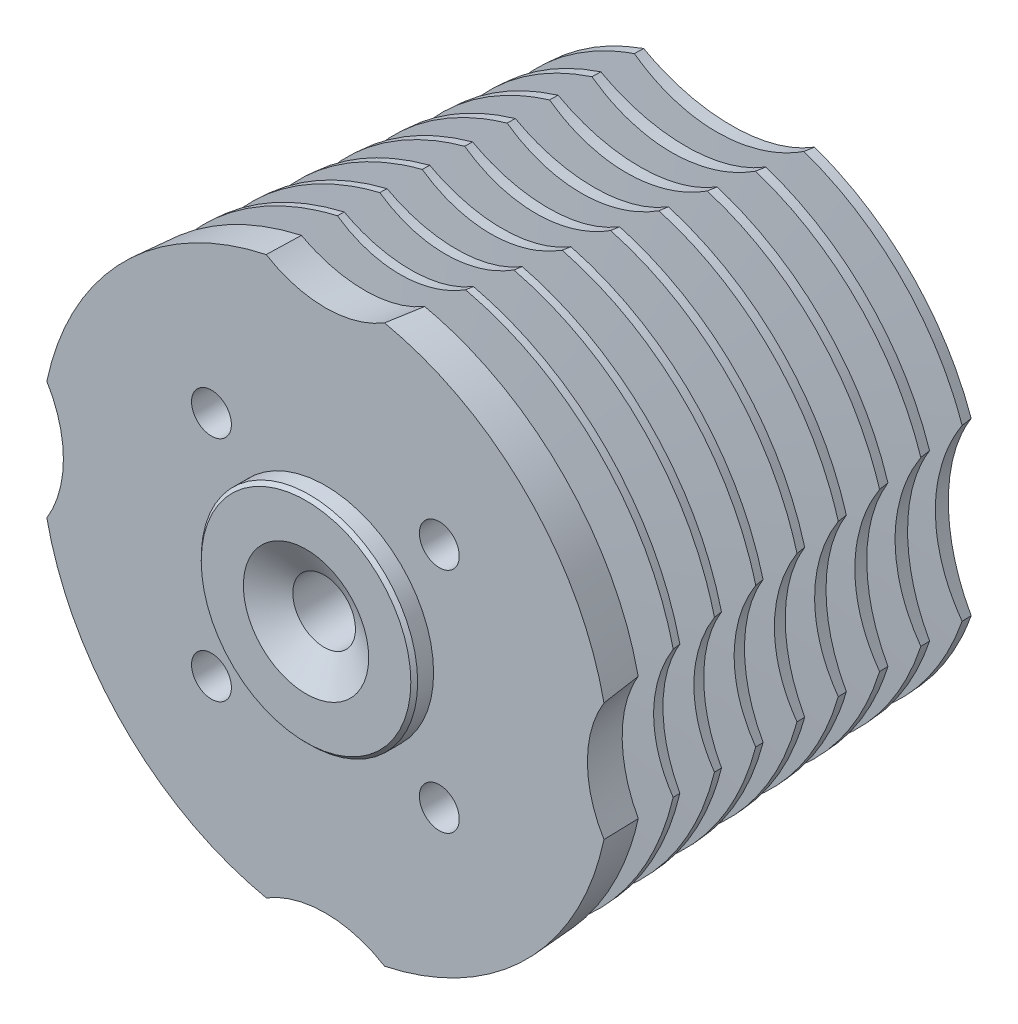
SolidWorks part; units mm, degrees
ref_plane "Face" through (0, 0, 0) normal (0, 0, 1) x (1, 0, 0)
ref_plane "Dessus" through (0, 0, 0) normal (0, 1, 0) x (1, 0, 0)
ref_plane "Droite" through (0, 0, 0) normal (1, 0, 0) x (0, 0, -1)
sketch "Esquisse1" plane through (0, 0, 0) normal (0, 0, 1) x (1, 0, 0)
  circle A0 centre (0, 0) radius 9.5
  dimension "D1" = 19
extrude "Base-Extrusion" add sketch "Esquisse1" along normal blind 1.7
sketch "Esquisse2" plane through (0, 0, 0) normal (0, 0, -1) x (-1, 0, 0)
  arc A0 (24.4545, 5.1938) -> (5.1938, 24.4545) centre (0, 0) ccw
  arc A1 (-5.1938, 24.4545) -> (5.1938, 24.4545) centre (0, 33) ccw
  arc A2 (5.1938, -24.4545) -> (-5.1938, -24.4545) centre (0, -33) ccw
  arc A3 (24.4545, 5.1938) -> (24.4545, -5.1938) centre (33, 0) ccw
  arc A4 (-24.4545, -5.1938) -> (-24.4545, 5.1938) centre (-33, 0) ccw
  arc A5 (-5.1938, 24.4545) -> (-24.4545, 5.1938) centre (0, 0) ccw
  arc A6 (-24.4545, -5.1938) -> (-5.1938, -24.4545) centre (0, 0) ccw
  arc A7 (5.1938, -24.4545) -> (24.4545, -5.1938) centre (0, 0) ccw
  dimension "D1" = 50
  dimension "D2" = 20
  dimension "D3" = 33
  dimension "D4" = 33
  dimension "D5" = 66
  dimension "D6" = 66
ref_plane "Plan1" through (0, 0, -36) normal (0, 0, 1) x (1, 0, 0)
sketch "Esquisse3" plane through (0, 0, -36) normal (0, 0, 1) x (1, 0, 0)
  arc A0 (7.5351, -21.2008) -> (21.2008, -7.5351) centre (0, 0) ccw
  arc A1 (-21.2008, -7.5351) -> (-21.2008, 7.5351) centre (-33, 0) ccw
  arc A2 (-7.5351, 21.2008) -> (7.5351, 21.2008) centre (0, 33) ccw
  arc A3 (21.2008, 7.5351) -> (21.2008, -7.5351) centre (33, 0) ccw
  arc A4 (7.5351, -21.2008) -> (-7.5351, -21.2008) centre (0, -33) ccw
  arc A5 (21.2008, 7.5351) -> (7.5351, 21.2008) centre (0, 0) ccw
  arc A6 (-7.5351, 21.2008) -> (-21.2008, 7.5351) centre (0, 0) ccw
  arc A7 (-21.2008, -7.5351) -> (-7.5351, -21.2008) centre (0, 0) ccw
  dimension "D1" = 45
  dimension "D2" = 28
loft "Boss.-Lissage1" add profiles "Esquisse2", "Esquisse3"
sketch "Esquisse4" plane through (0, 0, -36) normal (0, 0, -1) x (-1, 0, 0)
  line L0 (-8.8549, 14.5117) -> (-2.8725, 8.5293)
  line L1 (-14.5117, 8.8549) -> (-8.5293, 2.8725)
  line L2 (8.5293, -2.8725) -> (14.5117, -8.8549)
  line L3 (8.8549, 14.5117) -> (2.8725, 8.5293)
  line L4 (14.5117, 8.8549) -> (8.5293, 2.8725)
  line L5 (-8.5293, -2.8725) -> (-14.5117, -8.8549)
  line L6 (-2.8725, -8.5293) -> (-8.8549, -14.5117)
  line L7 (2.8725, -8.5293) -> (8.8549, -14.5117)
  arc A0 (-8.5293, 2.8725) -> (-8.5293, -2.8725) centre (0, 0) ccw
  arc A1 (8.8549, -14.5117) -> (14.5117, -8.8549) centre (0, 0) ccw
  arc A2 (-14.5117, -8.8549) -> (-8.8549, -14.5117) centre (0, 0) ccw
  arc A3 (-8.8549, 14.5117) -> (-14.5117, 8.8549) centre (0, 0) ccw
  arc A4 (14.5117, 8.8549) -> (8.8549, 14.5117) centre (0, 0) ccw
  arc A5 (-2.8725, -8.5293) -> (2.8725, -8.5293) centre (0, 0) ccw
  arc A6 (8.5293, -2.8725) -> (8.5293, 2.8725) centre (0, 0) ccw
  arc A7 (2.8725, 8.5293) -> (-2.8725, 8.5293) centre (0, 0) ccw
  dimension "D1" = 18
  dimension "D3" = 34
  dimension "D2" = 8
  dimension "D4" = 4
  dimension "D6" = 4
  dimension "D7" = 8
extrude "Enlèv. mat.-Extru.1" cut sketch "Esquisse4" against normal blind 32
sketch "Esquisse6" plane through (0, 0, 0) normal (0, 1, 0) x (1, 0, 0)
  line L1 (-13, 38) -> (-29.9757, 39)
  line L2 (-29.9757, 39) -> (-29.9757, 35)
  line L3 (-13, 36) -> (-29.9757, 35)
  line L4 (-13, 38) -> (-13, 36)
  line L5 (0, 4) -> (0, 36) construction
  line L6 (0, 0) -> (0, 35.1503) construction
  line L7 (0, -1.7) -> (0, 0) construction
  line L8 (-24.4545, 0) -> (-5.1938, 0) construction
  dimension "D1" = 2
  dimension "D2" = 4
  dimension "D3" = 13
  dimension "D4" = 36
revolve "Enlèvement de matière-Révolution2" cut sketch "Esquisse6" angle 360 about L6
pattern_linear "Répétition linéaire1" count 9 spacing 4 along (0, 0, 1) of "Enlèvement de matière-Révolution2"
chamfer "Chanfrein1" distance 0.3 angle 45 1 edges at (9.5, 0, 1.7)
sketch "Esquisse7" plane through (0, 0, -4) normal (0, 0, -1) x (-1, 0, 0)
  circle A0 centre (10, 10) radius 1.75
  dimension "D3" = 3.5
  dimension "D1" = 10
  dimension "D2" = 10
extrude "Enlèv. mat.-Extru.2" cut sketch "Esquisse7" against normal through all
pattern_circular "Répétition circulaire1" count 4 over 360 of "Enlèv. mat.-Extru.2"
hole_wizard "Perçage1" positions "Esquisse9" profile "Esquisse8" legacy
sketch "Esquisse9" plane through (0, 0, 1.7) normal (0, 0, 1) x (1, 0, 0)
  point P0 (0, 0)
sketch "Esquisse8" plane through (0, 0, 1.7) normal (1, 0, 0) x (0, -1, 0)
  line L0 (0, 0) -> (0, 100)
  line L1 (0, 100) -> (2.75, 100)
  line L2 (2.75, 100) -> (2.75, 1.5877)
  line L3 (2.75, 1.5877) -> (5.5, 0)
  line L4 (5.5, 0) -> (0, 0)
  line L5 (0, -6.4453) -> (0, 115.525) construction
  line L6 (-2.75, 1.5877) -> (-5.5, 0) construction
  dimension "Diamètre" = 5.5
  dimension "Profondeur" = 100
  dimension "Angle fraisé" = 120
  dimension "Diamètre fraisé" = 11
sketch "Esquisse10" plane through (0, 0, 1.7) normal (0, 0, 1) x (1, 0, 0)
  line L1 (0, -28.4478) -> (-30.1529, -28.4478)
  line L2 (0, -28.4478) -> (0, 29.121)
  line L3 (0, 29.121) -> (-30.1529, 29.121)
  line L4 (-30.1529, -28.4478) -> (-30.1529, 29.121)
extrude "Enlèv. mat.-Extru.3" [suppressed] cut sketch "Esquisse10" against normal through all
